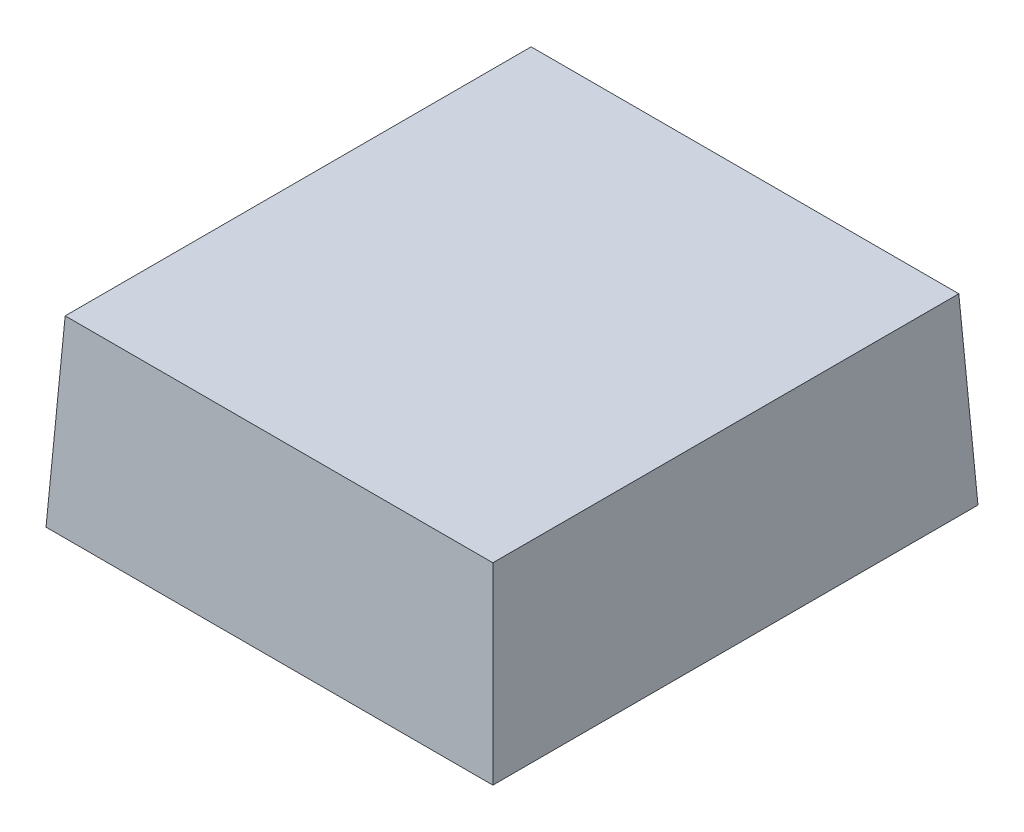
SolidWorks part; units mm, degrees
ref_plane "Front Plane" through (0, 0, 0) normal (0, 0, 1) x (1, 0, 0)
ref_plane "Top Plane" through (0, 0, 0) normal (0, 1, 0) x (1, 0, 0)
ref_plane "Right Plane" through (0, 0, 0) normal (1, 0, 0) x (0, 0, -1)
sketch "Sketch1" plane through (0, 0, 0) normal (0, 1, 0) x (1, 0, 0)
  line L1 (0, 0) -> (56.5, 0)
  line L2 (0, 0) -> (0, 61.34)
  line L3 (0, 61.34) -> (56.5, 61.34)
  line L4 (56.5, 0) -> (56.5, 61.34)
  dimension "D1" = 56.5
  dimension "D2" = 61.34
extrude "Boss-Extrude1" add sketch "Sketch1" along normal blind 23.14
draft "Draft1" type of draft neutral plane draft angle 3 faces to draft 4 face at (28.25, 11.57, 0) face at (0, 11.57, -30.67) face at (28.25, 11.57, -61.34) face at (56.5, 11.57, -30.67) neutral plane through (0, 0, 0) neutral plane normal (0, -1, 0) reverse direction yes parameters "D1"=3
